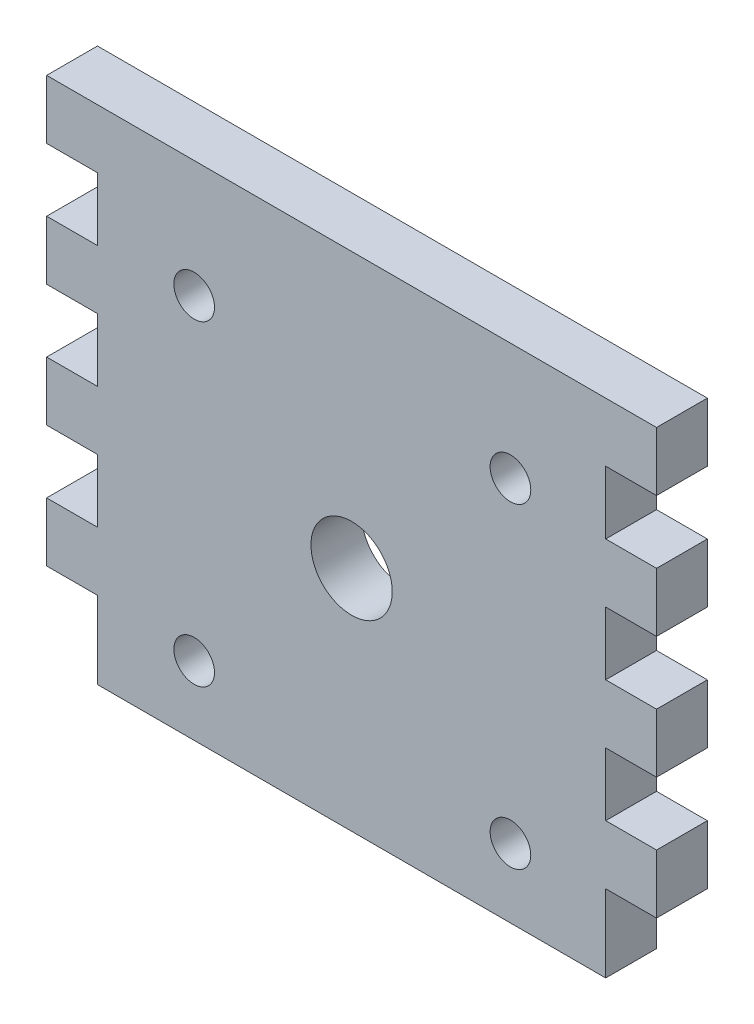
SolidWorks part; units mm, degrees
ref_plane "Front Plane" through (0, 0, 0) normal (0, 0, 1) x (1, 0, 0)
ref_plane "Top Plane" through (0, 0, 0) normal (0, 1, 0) x (1, 0, 0)
ref_plane "Right Plane" through (0, 0, 0) normal (1, 0, 0) x (0, 0, -1)
sketch "Sketch1" plane through (0, 0, 0) normal (0, 0, 1) x (1, 0, 0)
  line L1 (-37.8801, 17.0433) -> (38.3199, 17.0433)
  line L2 (-37.8801, 17.0433) -> (-37.8801, -59.1567)
  line L3 (-37.8801, -59.1567) -> (38.3199, -59.1567)
  line L4 (38.3199, 17.0433) -> (38.3199, -59.1567)
  dimension "D1" = 76.2
  dimension "D2" = 76.2
extrude "Boss-Extrude1" add sketch "Sketch1" along normal blind 6.35
sketch "Sketch2" plane through (0, 0, 6.35) normal (0, 0, 1) x (1, 0, 0)
  line L0 (-37.8801, 17.0433) -> (-31.5301, 17.0433)
  line L1 (38.3199, 17.0433) -> (-37.8801, 17.0433) construction
  line L2 (-31.5301, 17.0433) -> (-31.5301, 9.4233)
  line L3 (-31.5301, 9.4233) -> (-37.8801, 9.4233)
  line L4 (-37.8801, 17.0433) -> (-37.8801, -59.1567) construction
  line L5 (-37.8801, 9.4233) -> (-37.8801, 1.8033)
  line L6 (-37.8801, 1.8033) -> (-31.5301, 1.8033)
  line L7 (-31.5301, 1.8033) -> (-31.5301, -5.8167)
  line L8 (-31.5301, -5.8167) -> (-37.8801, -5.8167)
  line L9 (-37.8801, -5.8167) -> (-37.8801, -13.4367)
  line L10 (-37.8801, -13.4367) -> (-31.5301, -13.4367)
  line L11 (-31.5301, -13.4367) -> (-31.5301, -21.0567)
  line L12 (-31.5301, -21.0567) -> (-37.8801, -21.0567)
  line L13 (-37.8801, -21.0567) -> (-46.7258, -21.0567)
  line L14 (-37.8801, -21.0567) -> (-37.8801, -28.6767) [skipped]
  line L15 (-46.7258, -21.0567) -> (-46.7258, 17.0433)
  line L16 (-46.7258, 17.0433) -> (-37.8801, 17.0433)
  line L19 (47.1657, -21.0567) -> (47.1657, 17.0433)
  line L20 (38.3199, -21.0567) -> (47.1657, -21.0567)
  line L21 (31.9699, -21.0567) -> (38.3199, -21.0567)
  line L22 (31.9699, -13.4367) -> (31.9699, -21.0567)
  line L23 (38.3199, -13.4367) -> (31.9699, -13.4367)
  line L24 (38.3199, -5.8167) -> (38.3199, -13.4367)
  line L25 (31.9699, -5.8167) -> (38.3199, -5.8167)
  line L26 (31.9699, 1.8033) -> (31.9699, -5.8167)
  line L27 (38.3199, 1.8033) -> (31.9699, 1.8033)
  line L28 (38.3199, 9.4233) -> (38.3199, 1.8033)
  line L29 (31.9699, 9.4233) -> (38.3199, 9.4233)
  line L30 (31.9699, 17.0433) -> (31.9699, 9.4233)
  line L31 (38.3199, 17.0433) -> (31.9699, 17.0433)
  line L32 (47.1657, 17.0433) -> (38.3199, 17.0433)
  dimension "D1" = 7.62
  dimension "D2" = 7.62
  dimension "D3" = 6.35
  dimension "D4" = 6.35
  dimension "D6" = 38.1
  dimension "D5" = 3
extrude "Cut-Extrude1" cut sketch "Sketch2" against normal blind 6.35
sketch "Sketch3" plane through (0, 0, 6.35) normal (0, 0, 1) x (1, 0, 0)
  line L1 (-31.5301, -21.0567) -> (-37.8801, -21.0567)
  line L2 (-31.5301, -21.0567) -> (-31.5301, -59.1567)
  line L3 (-31.5301, -59.1567) -> (-37.8801, -59.1567)
  line L4 (-37.8801, -21.0567) -> (-37.8801, -59.1567)
  line L5 (31.9699, -21.0567) -> (38.3199, -21.0567)
  line L6 (31.9699, -21.0567) -> (31.9699, -59.1567)
  line L7 (31.9699, -59.1567) -> (38.3199, -59.1567)
  line L8 (38.3199, -21.0567) -> (38.3199, -59.1567)
extrude "Cut-Extrude2" cut sketch "Sketch3" against normal blind 6.35
sketch "Sketch4" plane through (0, 0, 6.35) normal (0, 0, 1) x (1, 0, 0)
  line L0 (-31.5301, -13.4367) -> (-31.5301, -21.0567)
  line L1 (-31.5301, -59.1567) -> (-31.5301, -13.4367) construction
  line L2 (-31.5301, -21.0567) -> (-37.8801, -21.0567)
  line L3 (-37.8801, -21.0567) -> (-37.8801, -28.6767)
  line L4 (-37.8801, -28.6767) -> (-31.5301, -28.6767)
  line L5 (-31.5301, -21.0567) -> (-31.5301, -28.6767)
  line L6 (0.2199, 17.0433) -> (0.2199, -59.1567)
  line L7 (31.9699, 17.0433) -> (-31.5301, 17.0433) construction
  line L8 (-31.5301, -59.1567) -> (31.9699, -59.1567) construction
  line L9 (31.9699, -21.0567) -> (38.3199, -21.0567)
  line L10 (38.3199, -21.0567) -> (38.3199, -28.6767)
  line L11 (38.3199, -28.6767) -> (31.9699, -28.6767)
  line L12 (31.9699, -21.0567) -> (31.9699, -28.6767)
  line M6 (-31.5301, -13.4367) -> (-31.5301, -59.1567)
  line M8 (31.9699, -59.1567) -> (31.9699, -13.4367)
  dimension "D1" = 7.62
  dimension "D2" = 7.62
  dimension "D3" = 6.35
  dimension "D4" = 6.35
extrude "Boss-Extrude3" add sketch "Sketch4" against normal blind 6.35 contours L3 L4 L2 M6 | L11 L10 L9 M8 region at (-34.7051, -24.8667, 6.35) region at (35.1449, -24.8667, 6.35)
sketch "Sketch5" plane through (0, 17.0433, 0) normal (0, 1, 0) x (1, 0, 0)
  line L1 (-31.5301, 0) -> (31.9699, 0)
  line L2 (-31.5301, 0) -> (-31.5301, -6.35)
  line L3 (-31.5301, -6.35) -> (31.9699, -6.35)
  line L4 (31.9699, 0) -> (31.9699, -6.35)
extrude "Cut-Extrude3" cut sketch "Sketch5" against normal blind 7.62
sketch "Sketch6" plane through (0, 0, 6.35) normal (0, 0, 1) x (1, 0, 0)
  line L0 (-31.5301, -59.1567) -> (31.9699, -59.1567) construction
  line L1 (-19.4468, -5.1999) -> (0.2199, -24.8667) construction
  line L2 (0.2199, -24.8667) -> (-37.8801, -24.8667) construction
  circle A0 centre (0.2199, -24.8667) radius 5.08
  circle A5 centre (-19.4468, -5.1999) radius 2.54
  circle A6 centre (20.0663, -5.1999) radius 2.54
  circle A7 centre (20.0663, -44.7131) radius 2.54
  circle A8 centre (-19.4468, -44.7131) radius 2.54
  point P16 (0.2825, -24.9292)
  point P18 (0.3097, -24.9565)
  dimension "D3" = 10.16
  dimension "D6" = 4
  dimension "D8" = 5.08
  dimension "D1" = 34.29
  dimension "D2" = 31.75
  dimension "D4" = 45
  dimension "D5" = 27.813
extrude "Cut-Extrude4" cut sketch "Sketch6" against normal through all
sketch "Sketch7" plane through (0, 0, 6.35) normal (0, 0, 1) x (1, 0, 0)
  line L0 (-31.5301, -28.6767) -> (-31.5301, -36.2967)
  line L1 (-31.5301, -59.1567) -> (-31.5301, -28.6767) construction
  line L2 (-31.5301, -36.2967) -> (-37.8801, -36.2967)
  line L3 (31.9699, -28.6767) -> (31.9699, -36.2967)
  line L4 (31.9699, -28.6767) -> (31.9699, -59.1567) construction
  line L5 (31.9699, -36.2967) -> (38.3199, -36.2967)
  line L6 (-37.8801, -36.2967) -> (-37.8801, -43.9167)
  line L7 (-37.8801, -43.9167) -> (-31.5301, -43.9167)
  line L8 (38.3199, -36.2967) -> (38.3199, -43.9167)
  line L9 (38.3199, -43.9167) -> (31.9699, -43.9167)
  line L12 (-31.5301, -43.9167) -> (-31.5301, -59.1567)
  line M27 (-31.5301, -28.6767) -> (-31.5301, -59.1567)
  line M29 (31.9699, -59.1567) -> (31.9699, -28.6767)
  dimension "D1" = 7.62
  dimension "D2" = 6.35
  dimension "D3" = 7.62
  dimension "D4" = 6.35
  dimension "D5" = 7.62
  dimension "D6" = 7.62
  dimension "D7" = 6.35
  dimension "D8" = 6.35
extrude "Boss-Extrude4" add sketch "Sketch7" against normal blind 6.35 contours L6 L7 L2 M27 | L9 L8 L5 M29 region at (-34.7051, -40.1067, 6.35) region at (35.1449, -40.1067, 6.35)
sketch "Sketch8" plane through (0, 0, 6.35) normal (0, 0, 1) x (1, 0, 0)
sketch "Sketch9" plane through (0, 0, 6.35) normal (0, 0, 1) x (1, 0, 0)
  line L0 (-31.5301, -43.9167) -> (-31.5301, -59.1567)
  line L1 (-31.5301, -59.1567) -> (31.9699, -59.1567)
  line L2 (31.9699, -59.1567) -> (31.9699, -43.9167)
  line L3 (31.9699, -43.9167) -> (31.9699, -59.1567) construction
  line L6 (-31.5301, -53.3208) -> (31.9699, -53.3208)
  line L7 (-31.5301, -53.3208) -> (-31.5301, -59.1567)
  line L8 (-31.5301, -59.1567) -> (31.9699, -59.1567)
  line L9 (31.9699, -53.3208) -> (31.9699, -59.1567)
  line M28 (-31.5301, -59.1567) -> (31.9699, -59.1567)
  line M29 (31.9699, -59.1567) -> (31.9699, -43.9167)
extrude "Cut-Extrude5" cut sketch "Sketch9" against normal blind 6.35 contours L6 L0 M28 M29 region at (0.2199, -56.2388, 6.35)
sketch "Sketch10" plane through (0, 1.8033, 0) normal (0, -1, 0) x (1, 0, 0)
  line L0 (38.3199, 0) -> (38.3199, 6.35) construction
  line L1 (31.9699, 0) -> (38.3199, 0)
  line L2 (31.9699, 0) -> (31.9699, 6.35)
  line L3 (31.9699, 6.35) -> (38.3199, 6.35)
  line L4 (38.3199, 0) -> (38.3199, 6.35)
  line L5 (38.3199, 6.35) -> (31.9699, 6.35) construction
  point P9 (31.9699, 0)
  point P10 (31.9699, 0)
extrude "Boss-Extrude5" add sketch "Sketch10" along normal blind 55.118
sketch "Sketch11" plane through (0, 1.8033, 0) normal (0, -1, 0) x (1, 0, 0)
  line L1 (-31.5301, 0) -> (-37.8801, 0)
  line L2 (-31.5301, 0) -> (-31.5301, 6.35)
  line L3 (-31.5301, 6.35) -> (-37.8801, 6.35)
  line L4 (-37.8801, 0) -> (-37.8801, 6.35)
extrude "Boss-Extrude6" add sketch "Sketch11" along normal blind 55.118
sketch "Sketch12" plane through (0, 0, 6.35) normal (0, 0, 1) x (1, 0, 0)
  line L0 (-37.8801, 9.4233) -> (-37.8801, 2.0573)
  line L1 (-37.8801, 9.4233) -> (-37.8801, -53.3147) construction
  line L2 (-37.8801, 2.0573) -> (-31.5301, 2.0573)
  line L3 (-31.5301, 2.0573) -> (-31.5301, -5.8167)
  line L4 (-31.5301, -5.8167) -> (-37.8801, -5.8167)
  line L5 (-37.8801, -5.8167) -> (-37.8801, -13.1827)
  line L6 (-37.8801, -13.1827) -> (-31.5301, -13.1827)
  line L7 (-31.5301, -13.1827) -> (-31.5301, -21.0567)
  line L8 (-31.5301, -21.0567) -> (-37.8801, -21.0567)
  line L9 (-37.8801, -21.0567) -> (-37.8801, -28.4227)
  line L10 (-37.8801, -28.4227) -> (-31.5301, -28.4227)
  line L11 (-31.5301, -28.4227) -> (-31.5301, -36.2967)
  line L12 (-31.5301, -36.2967) -> (-37.8801, -36.2967)
  line L13 (-37.8801, -36.2967) -> (-37.8801, -43.6627)
  line L14 (-37.8801, -43.6627) -> (-31.5301, -43.6627)
  line L15 (-31.5301, -43.6627) -> (-31.5301, -51.5367)
  line L16 (-31.5301, -51.5367) -> (-37.8801, -51.5367)
  line L17 (-37.8801, 9.4233) -> (-56.0123, 9.4233)
  line L18 (-56.0123, 9.4233) -> (-56.0123, -53.8176)
  line L19 (-56.0123, -53.8176) -> (-37.8801, -51.5367)
  line L20 (0.2199, 9.4233) -> (0.2199, -53.3208)
  line L21 (-37.8801, 9.4233) -> (38.3199, 9.4233) construction
  line L22 (-31.5301, -53.3208) -> (31.9699, -53.3208) construction
  line L23 (56.4521, 9.4233) -> (56.4521, -53.8176)
  line L24 (38.3199, 9.4233) -> (56.4521, 9.4233)
  line L25 (38.3199, 9.4233) -> (38.3199, 2.0573)
  line L26 (38.3199, 2.0573) -> (31.9699, 2.0573)
  line L27 (31.9699, 2.0573) -> (31.9699, -5.8167)
  line L28 (31.9699, -5.8167) -> (38.3199, -5.8167)
  line L29 (38.3199, -5.8167) -> (38.3199, -13.1827)
  line L30 (38.3199, -13.1827) -> (31.9699, -13.1827)
  line L31 (31.9699, -13.1827) -> (31.9699, -21.0567)
  line L32 (31.9699, -21.0567) -> (38.3199, -21.0567)
  line L33 (38.3199, -21.0567) -> (38.3199, -28.4227)
  line L34 (38.3199, -28.4227) -> (31.9699, -28.4227)
  line L35 (31.9699, -28.4227) -> (31.9699, -36.2967)
  line L36 (31.9699, -36.2967) -> (38.3199, -36.2967)
  line L37 (38.3199, -36.2967) -> (38.3199, -43.6627)
  line L38 (38.3199, -43.6627) -> (31.9699, -43.6627)
  line L39 (31.9699, -43.6627) -> (31.9699, -51.5367)
  line L40 (31.9699, -51.5367) -> (38.3199, -51.5367)
  line L41 (56.4521, -53.8176) -> (38.3199, -51.5367)
  line M26 (38.3199, -53.3147) -> (38.3199, 9.4233)
  line M28 (-37.8801, 9.4233) -> (-37.8801, -53.3147)
  dimension "D1" = 7.366
  dimension "D2" = 7.874
  dimension "D3" = 6.35
  dimension "D4" = 4
extrude "Cut-Extrude7" cut sketch "Sketch12" against normal blind 55.118 contours L18 L19 L17 M28 | L41 L23 L24 M26 | L39 L40 L38 M26 | L35 L36 L34 M26 | L31 L32 L30 M26 | L27 L28 L26 M26 | L4 L3 L2 M28 | L8 L7 L6 M28 | L12 L11 L10 M28 | L16 L15 L14 M28 region at (-47.0017, -21.6304, 6.35) region at (-34.7051, -1.8797, 6.35) region at (-34.7051, -17.1197, 6.35) region at (-34.7051, -47.5997, 6.35) region at (-34.7051, -32.3597, 6.35) region at (47.4415, -21.6304, 6.35) region at (35.1449, -47.5997, 6.35) region at (35.1449, -1.8797, 6.35) region at (35.1449, -32.3597, 6.35) region at (35.1449, -17.1197, 6.35)
sketch "Sketch13" plane through (0, -51.5367, 0) normal (0, 1, 0) x (1, 0, 0)
  line L1 (-37.8801, 0) -> (-31.5301, 0)
  line L2 (-37.8801, 0) -> (-37.8801, -6.35)
  line L3 (-37.8801, -6.35) -> (-31.5301, -6.35)
  line L4 (-31.5301, 0) -> (-31.5301, -6.35)
  line L5 (31.9699, 0) -> (38.3199, 0)
  line L6 (31.9699, 0) -> (31.9699, -6.35)
  line L7 (31.9699, -6.35) -> (38.3199, -6.35)
  line L8 (38.3199, 0) -> (38.3199, -6.35)
extrude "Cut-Extrude8" cut sketch "Sketch13" against normal blind 55.118
